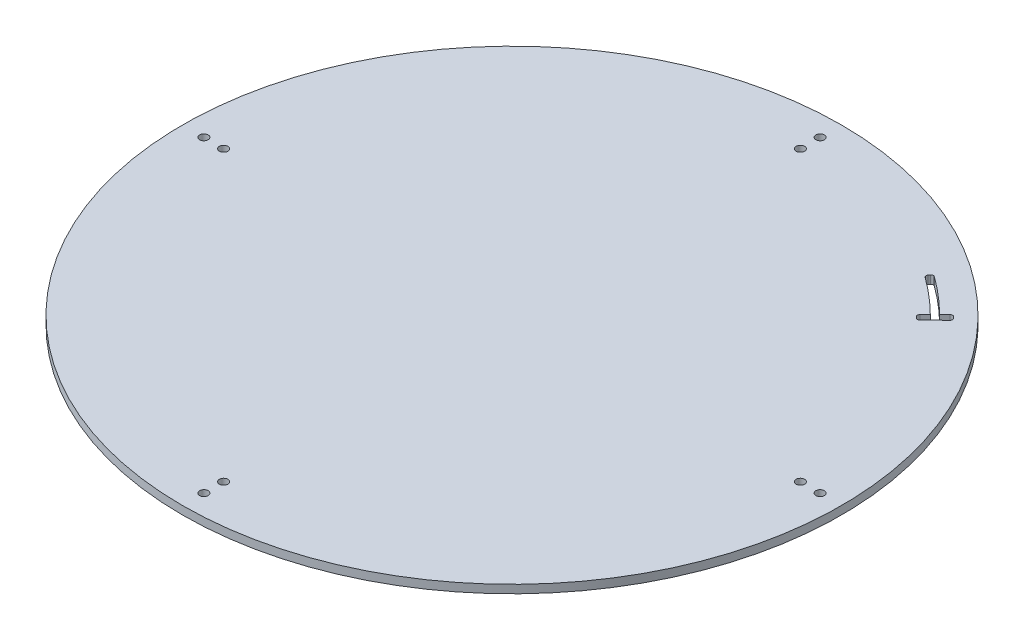
SolidWorks part; units mm, degrees
ref_plane "前视基准面" through (0, 0, 0) normal (0, 0, 1) x (1, 0, 0)
ref_plane "上视基准面" through (0, 0, 0) normal (0, 1, 0) x (1, 0, 0)
ref_plane "右视基准面" through (0, 0, 0) normal (1, 0, 0) x (0, 0, -1)
ref_axis "中心轴" through (0, -55, 0) along (0, 1, 0)
sketch "草图1" plane through (0, 0, 0) normal (0, 1, 0) x (1, 0, 0)
  circle A0 centre (0, 0) radius 200
extrude "主体" add sketch "草图1" along normal blind 5
sketch "草图2" plane through (0, 5, 0) normal (0, 1, 0) x (1, 0, 0)
  line L0 (0, 0) -> (0, 120.98) construction
  circle A0 centre (0, 0) radius 200
  circle A1 centre (0, 0) radius 187 construction
  circle A2 centre (0, 0) radius 200 construction
  circle A3 centre (0, 0) radius 175 construction
  circle A6 centre (0, -175) radius 2.6
  circle A7 centre (0, -187) radius 2.6
extrude "切除-拉伸3" cut sketch "草图2" against normal up to next contours A6 | A7 region at (0, 5, 175) region at (0, 5, 187)
pattern_circular "阵列(圆周)1" count 4 over 360 about axis through (0, -55, 0) along (0, 1, 0) of "切除-拉伸3"
sketch "草图4" plane through (0, 0, 0) normal (0.7071, 0, 0.7071) x (0.7071, 0, -0.7071)
  line L1 (180, 10.5) -> (183, 10.5) construction
  line L2 (180, 10.5) -> (180, 0) construction
  line L3 (180, 0) -> (183, 0) construction
  line L4 (183, 10.5) -> (183, 0) construction
  line L5 (183.5, 11) -> (183.5, -0.5)
  line L6 (179.5, -0.5) -> (183.5, -0.5)
  line L7 (179.5, 11) -> (179.5, -0.5)
  line L8 (179.5, 11) -> (183.5, 11)
  dimension "D1" = 0.5
revolve "切除-旋转3" cut sketch "草图4" angle 9.5 about axis through (0, -55, 0) along (0, 1, 0) other way angle 0.5
fillet "圆角2" radius 1.5 2 edges at (104.2362, 2.5, -146.1337) (106.559, 2.5, -149.3902)
sketch "草图6" plane through (0, 5, 0) normal (0, 1, 0) x (1, 0, 0)
  line L0 (123.0366, 123.0366) -> (133.6432, 133.6432) construction
  line L1 (126.2395, 121.9081) -> (134.8719, 130.2443) construction
  line L4 (135.9552, 131.2904) -> (125.1651, 120.8706) construction
  line L6 (124.0927, 124.0927) -> (132.5783, 132.5783) construction
  line L8 (122.329, 123.0361) -> (133.6427, 134.3498)
  line L9 (136.6617, 131.2776) -> (125.1523, 120.1631)
  line L10 (139.3566, 127.8395) -> (130.2521, 137.1042) construction
  line L11 (121.0961, 125.0207) -> (127.1151, 118.8957) construction
  arc A0 (135.9552, 131.2904) -> (133.6432, 133.6432) centre (0, 0) ccw construction
  arc A1 (125.1651, 120.8706) -> (123.0366, 123.0366) centre (0, 0) ccw construction
  arc A4 (136.6617, 131.2776) -> (133.6427, 134.3498) centre (0, 0) ccw
  arc A5 (125.1523, 120.1631) -> (122.329, 123.0361) centre (0, 0) ccw
  dimension "D1" = 0.5
extrude "开孔" cut sketch "草图6" against normal up to next
fillet "圆角1" radius 1.5 4 edges at (125.1523, 2.5, -120.1631) (136.6617, 2.5, -131.2776) (133.6427, 2.5, -134.3498) (122.329, 2.5, -123.0361)
